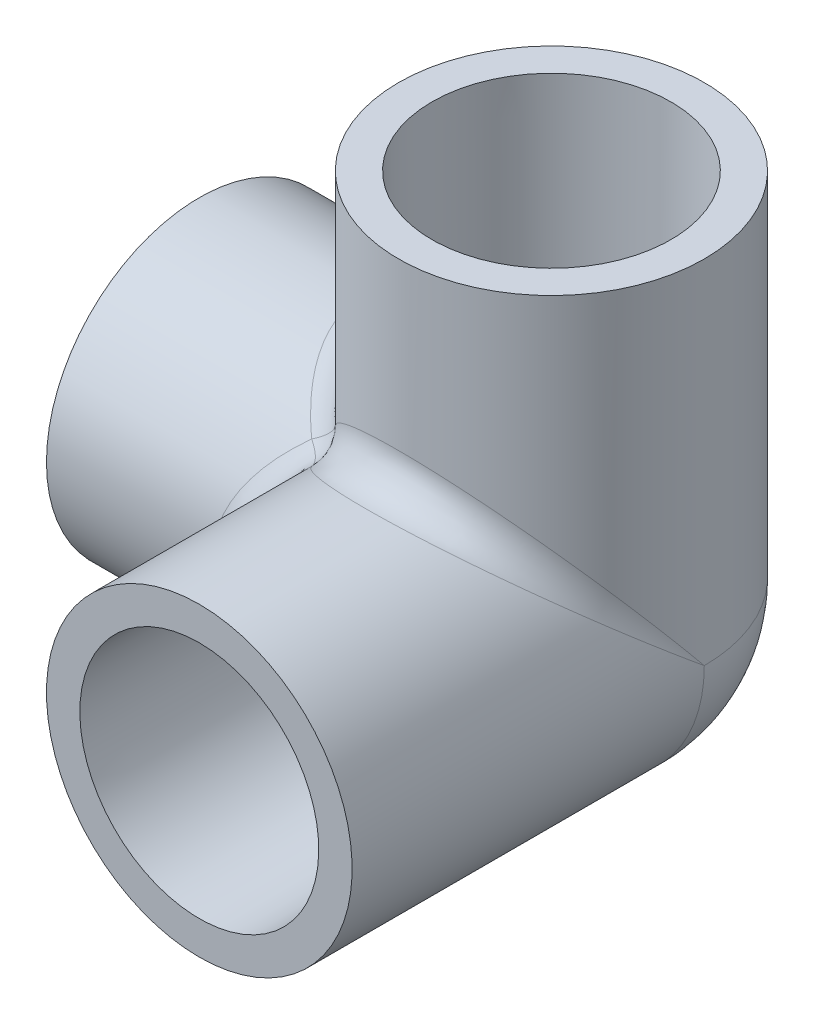
SolidWorks part; units mm, degrees
ref_plane "Front Plane" through (0, 0, 0) normal (0, 0, 1) x (1, 0, 0)
ref_plane "Top Plane" through (0, 0, 0) normal (0, 1, 0) x (1, 0, 0)
ref_plane "Right Plane" through (0, 0, 0) normal (1, 0, 0) x (0, 0, -1)
sketch "Sketch0" plane through (0, 0, 0) normal (0, 0, 1) x (1, 0, 0)
  line L0 (-31.75, 0) -> (0, 0) construction
  line L1 (0, 0) -> (0, 31.75) construction
  line L2 (-12.7, 0) -> (0, 0) construction
  line L3 (0, 0) -> (0, 12.7) construction
  line L4 (-31.75, 13.7795) -> (-31.75, -13.7795) construction
  line L5 (-12.7, 10.6172) -> (-31.75, 10.7696) construction
  line L6 (-12.7, 10.6172) -> (-12.7, -10.6172) construction
  line L7 (-12.7, -10.6172) -> (-31.75, -10.7696) construction
  line L8 (-31.75, 10.7696) -> (-31.75, -10.7696) construction
  line L9 (-13.7795, 31.75) -> (13.7795, 31.75) construction
  line L10 (-10.7696, 31.75) -> (10.7696, 31.75) construction
  line L11 (10.7696, 31.75) -> (10.6172, 12.7) construction
  line L12 (10.6172, 12.7) -> (-10.6172, 12.7) construction
  line L13 (-10.6172, 12.7) -> (-10.7696, 31.75) construction
  line L14 (-12.7, 7.8994) -> (-12.7, -7.8994) construction
  line L18 (-7.8994, 12.7) -> (7.8994, 12.7) construction
  dimension "H" = 31.75
  dimension "G" = 12.7
  dimension "M" = 27.559
  dimension "OD A" = 21.5392
  dimension "OD B" = 21.2344
  dimension "ID" = 15.7988
sketch "Sketch1" plane through (0, 0, 0) normal (0, 0, 1) x (1, 0, 0)
  line L0 (-31.75, 0) -> (13.7795, 0)
  line L1 (-31.75, 0) -> (-31.75, -13.7795)
  line L2 (-31.75, -13.7795) -> (0, -13.7795)
  arc A0 (0, -13.7795) -> (13.7795, 0) centre (0, 0) ccw
  dimension "D1" = 45.5295
revolve "Revolve1" add sketch "Sketch1" angle 360 about L0
sketch "Sketch2" plane through (0, 0, 0) normal (0, 0, 1) x (1, 0, 0)
  line L0 (13.7795, 31.75) -> (0, 31.75)
  line L4 (0, 31.75) -> (0, -13.7795)
  line L5 (13.7795, 0) -> (13.7795, 31.75)
  arc A0 (13.7795, 0) -> (0, -13.7795) centre (0, 0) cw
revolve "Revolve2" add sketch "Sketch2" angle 360 about L4
sketch "Sketch3" plane through (0, 0, 0) normal (1, 0, 0) x (0, 0, -1)
  line L0 (13.7795, 0) -> (-31.75, 0)
  line L1 (-31.75, 0) -> (-31.75, -13.7795)
  line L2 (-31.75, -13.7795) -> (0, -13.7795)
  arc A0 (0, -13.7795) -> (13.7795, 0) centre (0, 0) ccw
  dimension "D1" = 45.5295
revolve "Revolve3" add sketch "Sketch3" angle 360 about L0
sketch "Sketch4" plane through (0, 0, 0) normal (0, 0, 1) x (1, 0, 0)
  line L0 (-31.75, 0) -> (7.8994, 0)
  line L1 (-31.75, 13.7795) -> (-31.75, -13.7795) construction
  line L2 (0, -7.8994) -> (-12.7, -7.8994)
  line L3 (-12.7, -7.8994) -> (-12.7, -10.6172)
  line L4 (-12.7, -10.6172) -> (-31.75, -10.7696)
  line L5 (-31.75, -10.7696) -> (-31.75, 0)
  arc A0 (7.8994, 0) -> (0, -7.8994) centre (0, 0) cw
  dimension "D1" = 19.05
revolve "Cut-Revolve1" cut sketch "Sketch4" angle 360 about L0
sketch "Sketch5" plane through (0, 0, 0) normal (0, 0, 1) x (1, 0, 0)
  line L0 (0, 31.75) -> (0, -7.8994)
  line L1 (7.8994, 0) -> (7.8994, 12.7)
  line L2 (7.8994, 12.7) -> (10.6172, 12.7)
  line L3 (10.6172, 12.7) -> (10.7696, 31.75)
  line L4 (0, 31.75) -> (10.7696, 31.75)
  arc A0 (0, -7.8994) -> (7.8994, 0) centre (0, 0) ccw
revolve "Cut-Revolve2" cut sketch "Sketch5" angle 360 about L0
sketch "Sketch6" plane through (0, 0, 0) normal (1, 0, 0) x (0, 0, -1)
  line L0 (7.8994, 0) -> (-31.75, 0)
  line L1 (-31.75, 0) -> (-31.75, -10.7696)
  line L2 (-31.75, -10.7696) -> (-12.7, -10.6172)
  line L3 (-12.7, -10.6172) -> (-12.7, -7.8994)
  line L4 (-12.7, -7.8994) -> (0, -7.8994)
  line L5 (-7.8994, 0) -> (7.8994, 0) construction
  line L6 (-31.75, 13.7795) -> (-31.75, -13.7795) construction
  arc A0 (0, -7.8994) -> (7.8994, 0) centre (0, 0) ccw
  dimension "D1" = 19.05
revolve "Cut-Revolve3" cut sketch "Sketch6" angle 360 about L0
fillet "Fillet1" radius 3.0099 6 edges at (-12.7306, -5.2732, 12.7306) (5.2732, 12.7306, 12.7306) (-12.7306, 12.7306, -5.2732) (-7.2981, -3.023, 7.2981) (-7.2981, 7.2981, -3.023) (3.023, 7.2981, 7.2981)
equation "\"D1@Sketch3\" = \"D1@Sketch1\""
equation "\"D1@Sketch6\" = \"D1@Sketch4\""
equation "\"D1@Fillet1\" =  ( \"M@Sketch0\" - \"OD A@Sketch0\" )  / 2"
